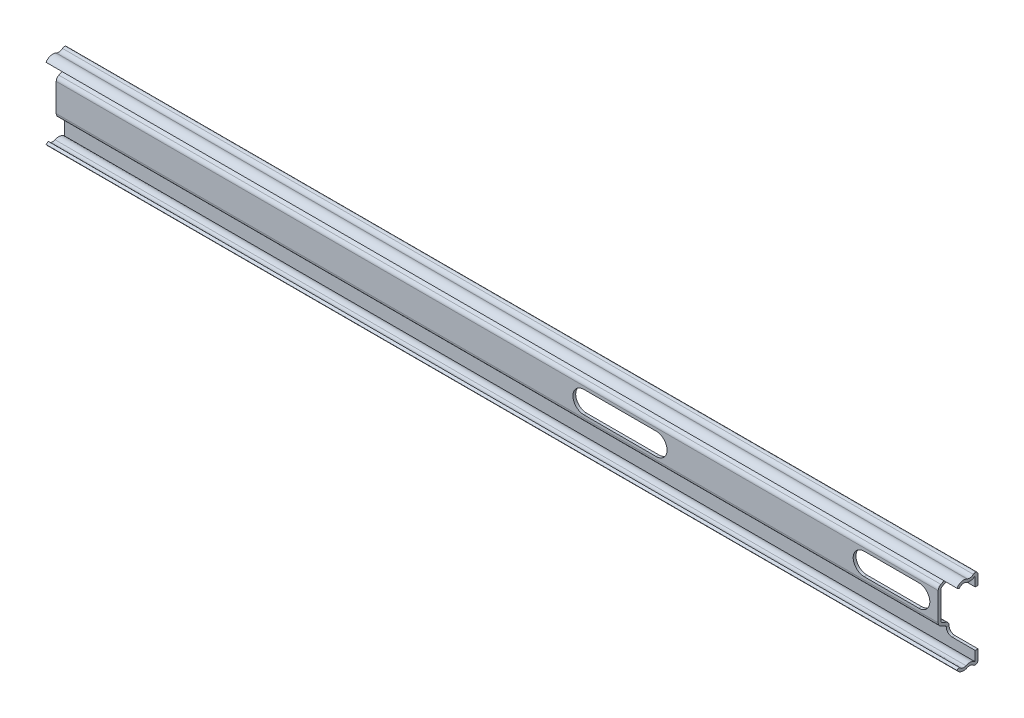
SolidWorks part; units mm, degrees
ref_plane "Front" through (0, 0, 0) normal (0, 0, 1) x (1, 0, 0)
ref_plane "Top" through (0, 0, 0) normal (0, 1, 0) x (1, 0, 0)
ref_plane "Right" through (0, 0, 0) normal (1, 0, 0) x (0, 0, -1)
sketch "Sketch1" plane through (0, 0, 0) normal (1, 0, 0) x (0, 0, -1)
  line L1 (5.6388, 0) -> (-5.6388, 0) construction
  line L4 (-4.1393, 22.8203) -> (-0.7433, 22.6989)
  line L5 (-1.1312, 21.5182) -> (-4.1819, 21.6273)
  line L6 (-4.445, 18.415) -> (-5.6388, 18.415)
  line L7 (-4.445, 21.3734) -> (-4.445, 18.415)
  line L8 (-5.6388, 18.415) -> (-5.6388, 21.3734)
  line L9 (3.9237, 21.6269) -> (0.7619, 21.5441)
  line L10 (5.6388, 0) -> (5.6388, 21.1191)
  line L11 (4.445, 21.1191) -> (4.445, 0)
  line L12 (5.6388, 0) -> (4.445, 0)
  line L13 (-0.7433, 22.6989) -> (3.8925, 22.8203)
  arc A0 (-4.445, 21.3734) -> (-4.1819, 21.6273) centre (-4.191, 21.3734) cw
  arc A1 (-5.6388, 21.3734) -> (-4.1393, 22.8203) centre (-4.191, 21.3734) cw
  arc A3 (3.9237, 21.6269) -> (4.445, 21.1191) centre (3.937, 21.1191) cw
  arc A4 (3.8925, 22.8203) -> (5.6388, 21.1191) centre (3.937, 21.1191) cw
  arc A5 (-1.1312, 21.5182) -> (0.7619, 21.5441) centre (-0.1524, 19.1744) cw
  dimension "D2" = 19.1744
  dimension "D7" = 0.254
  dimension "D8" = 0.508
  dimension "D6" = 2.54
  dimension "D9" = 1.1938
  dimension "D10" = 88.5
  dimension "D1" = 11.2776
  dimension "D3" = 5.7912
  dimension "D4" = 36.83
  dimension "D5" = 1.1938
  dimension "D11" = 87.953
  dimension "D12" = 45.6406
extrude "Extrude1" add sketch "Sketch1" along normal mid plane 400.05
ref_plane "Travel / 2" through (-403.225, 0, 0) normal (-1, 0, 0) x (0, 0, 1)
sketch "Sketch2" plane through (-403.225, 0, 0) normal (-1, 0, 0) x (0, 0, 1)
  line L0 (0.0254, 6.1159) -> (0.0254, 0)
  line L2 (-5.6388, 0) -> (5.6388, 0) construction
  line L3 (5.6388, 21.3734) -> (5.6388, 18.415) construction
  line L7 (-4.445, 21.1191) -> (-4.445, 0) construction
  line L8 (-5.6388, 0) -> (-5.6388, 21.1191) construction
  line L13 (-3.5306, 16.3766) -> (-3.5306, 9.5217)
  line L46 (-2.3867, 7.7262) -> (-0.4146, 6.8065)
  arc A0 (0.0254, 6.1159) -> (-0.4146, 6.8065) centre (-0.7366, 6.1159) ccw
  arc A1 (-1.5056, 17.2916) -> (1.2415, 16.9143) centre (0.1524, 19.1744) ccw
  arc A4 (1.1312, 21.5182) -> (-0.7619, 21.5441) centre (0.1524, 19.1744) ccw construction
  arc A19 (-3.5306, 9.5217) -> (-2.3867, 7.7262) centre (-1.5494, 9.5217) ccw
  arc A25 (-1.5056, 17.2916) -> (-3.5306, 16.3766) centre (-2.3114, 16.3766) ccw
  arc A51 (5.7404, 15.6277) -> (1.2415, 16.9143) centre (2.7686, 13.7451) ccw
  dimension "D2" = 8.4074
  dimension "D3" = 27.4903
  dimension "D6" = 1.9812
  dimension "D8" = 12.2319
  dimension "D10" = 2.5088
  dimension "D11" = 1.2192
  dimension "D4" = 0.762
  dimension "D5" = 4.4704
  dimension "D7" = 115
  dimension "D9" = 19.0435
  dimension "D13" = 11.3792
extrude "Middle Member" add sketch "Sketch2" against normal blind 400.05 separate body thin thin type one direction reverse wall 1.2192
ref_plane "Travel" through (-606.425, 0, 0) normal (-1, 0, 0) x (0, 0, 1)
sketch "Sketch3" plane through (-606.425, 0, 0) normal (-1, 0, 0) x (0, 0, 1)
  line L0 (1.2446, 0) -> (0.0254, 0) construction
  line L1 (-5.6388, 0) -> (-5.6388, 21.1191) construction
  line L56 (7.0612, 0) -> (7.0612, 10.6235)
  line L93 (5.5372, 12.1475) -> (5.1643, 12.1475)
  arc A0 (1.2082, 11.9072) -> (4.2365, 11.8325) centre (2.7686, 13.7451) ccw
  arc A29 (7.0612, 10.6235) -> (5.5372, 12.1475) centre (5.5372, 10.6235) ccw
  arc A53 (5.1643, 12.1475) -> (4.2365, 11.8325) centre (5.1643, 10.6235) ccw
  dimension "D1" = 1.524
  dimension "D4" = 1.524
  dimension "D5" = 2.411
  dimension "D2" = 12.7
  dimension "D3" = 12.1475
  dimension "D6" = 5.853
extrude "Drawer Member" add sketch "Sketch3" against normal blind 400.05 thin thin type one direction wall 1.397
sketch "Sketch6" plane through (0, 0, 7.0612) normal (0, 0, 1) x (1, 0, 0)
  line L1 (-606.425, 0) -> (-604.52, 0)
  line L2 (-606.425, 0) -> (-606.425, 12.1475)
  line L3 (-606.425, 12.1475) -> (-604.52, 12.1475)
  line L4 (-604.52, 0) -> (-604.52, 12.1475)
  line L5 (-206.375, 12.1475) -> (-606.425, 12.1475) construction
  line L7 (-606.425, 10.6235) -> (-606.425, 0) construction
  line L8 (-206.375, 0) -> (-606.425, 0) construction
  dimension "D1" = 1.905
extrude "Cut-Extrude1" cut sketch "Sketch6" against normal through all
sketch "Sketch8" plane through (0, 0, -4.445) normal (0, 0, 1) x (1, 0, 0)
  line L0 (190.3865, 7.6456) -> (191.8208, 7.493)
  line L1 (200.025, 12.2048) -> (190.6284, 12.2048)
  line L2 (191.8208, 7.493) -> (191.8208, 0)
  line L3 (200.025, 0) -> (-200.025, 0) construction
  line L4 (200.025, 21.1191) -> (200.025, 0) construction
  line L5 (200.025, 12.2048) -> (200.025, 0)
  line L6 (200.025, 0) -> (191.8208, 0)
  arc A0 (190.6284, 12.2048) -> (190.3865, 7.6456) centre (190.6284, 9.9188) ccw
  dimension "D3" = 9.9188
  dimension "D1" = 12.2048
  dimension "D2" = 8.2042
  dimension "D4" = 9.3966
  dimension "D5" = 7.493
extrude "Cut-Extrude2" cut sketch "Sketch8" against normal up to next (1.1938 mm away)
sketch "Sketch11" plane through (0, 0, 7.0612) normal (0, 0, 1) x (1, 0, 0)
  line L0 (-212.09, 5.9678) -> (-212.09, 0)
  line L8 (-206.375, 8.5893) -> (-212.2343, 7.2212)
  line L11 (-212.09, 0) -> (-206.375, 0)
  line L12 (-206.375, 0) -> (-206.375, 8.5893)
  arc A1 (-212.2343, 7.2212) -> (-212.09, 5.9678) centre (-212.0899, 6.6028) ccw
  dimension "D3" = 0.635
  dimension "D1" = 5.715
  dimension "D2" = 8.5893
  dimension "D4" = 5.9678
  dimension "D5" = 103.143
extrude "Cut-Extrude3" cut sketch "Sketch11" against normal up to next (1.397 mm away)
sketch "Sketch12" plane through (0, 0, 1.2446) normal (0, 0, 1) x (1, 0, 0)
  line L0 (-3.175, 12.065) -> (-13.335, 12.065)
  line L1 (-3.175, 16.3766) -> (-3.175, 9.5217) construction
  line L2 (-15.875, 9.525) -> (-15.875, 0)
  line L3 (-3.175, 0) -> (-403.225, 0) construction
  line L4 (-15.875, 0) -> (-3.175, 0)
  line L5 (-3.175, 0) -> (-3.175, 12.065)
  arc A0 (-13.335, 12.065) -> (-15.875, 9.525) centre (-13.335, 9.525) ccw
  point P11 (-15.875, 12.065)
  dimension "D3" = 2.54
  dimension "D1" = 12.7
  dimension "D2" = 12.065
extrude "Cut-Extrude4" cut sketch "Sketch12" against normal through all
sketch "Sketch13" plane through (0, 0, -4.445) normal (0, 0, 1) x (1, 0, 0)
  line L0 (-131.6367, 7.112) -> (-156.4652, 7.112)
  line L1 (191.8208, 0) -> (-200.025, 0) construction
  line L2 (-139.7266, 0) -> (-139.7266, 4.2392) construction
  line L3 (-182.5637, 10.287) -> (-131.6367, 10.287)
  line L4 (-200.025, 21.1191) -> (-200.025, 0) construction
  line L5 (-160.2752, 7.112) -> (-182.5637, 7.112)
  line L6 (-159.5132, 0) -> (-159.5132, 6.35)
  line L7 (-157.2272, 6.35) -> (-157.2272, 0)
  line L8 (-137.2501, 2.286) -> (-142.2031, 2.286)
  line L13 (-176.3026, 0) -> (-171.7306, 0)
  line L14 (-168.2, 0) -> (-161.85, 0)
  line L15 (-159.5132, 0) -> (-157.2272, 0)
  line L16 (-154.7126, 0) -> (-150.1406, 0)
  line L17 (-144.4891, 0) -> (-134.9641, 0)
  arc A1 (-182.5637, 10.287) -> (-182.5637, 7.112) centre (-182.5637, 8.6995) ccw
  arc A2 (-159.5132, 6.35) -> (-160.2752, 7.112) centre (-160.2752, 6.35) ccw
  arc A4 (-156.4652, 7.112) -> (-157.2272, 6.35) centre (-156.4652, 6.35) ccw
  arc A7 (-131.6367, 7.112) -> (-131.6367, 10.287) centre (-131.6367, 8.6995) ccw
  arc A8 (-161.85, 0) -> (-168.2, 0) centre (-165.025, 0) ccw
  arc A9 (-171.7306, 0) -> (-176.3026, 0) centre (-174.0166, 0) ccw
  arc A10 (-150.1406, 0) -> (-154.7126, 0) centre (-152.4266, 0) ccw
  arc A11 (-134.9641, 0) -> (-137.2501, 2.286) centre (-137.2501, 0) ccw
  arc A12 (-142.2031, 2.286) -> (-144.4891, 0) centre (-142.2031, 0) ccw
  dimension "D3" = 2.286
  dimension "D4" = 3.175
  dimension "D7" = 8.9916
  dimension "D8" = 21.59
  dimension "D9" = 34.29
  dimension "D10" = 0.762
  dimension "D11" = 17.5387
  dimension "D12" = 9.525
  dimension "D13" = 5.5118
  dimension "D14" = 35
  dimension "D1" = 3.175
  dimension "D2" = 50.927
  dimension "D5" = 2.286
  dimension "D6" = 10.287
extrude "Cut-Extrude5" cut sketch "Sketch13" against normal up to next (1.1938 mm away)
sketch "Sketch32" plane through (0, 0, -5.6388) normal (0, 0, -1) x (-1, 0, 0)
  line L0 (19.5625, 0) -> (29.0875, 0)
  line L1 (33.85, 0) -> (40.2, 0)
  line L2 (43.6925, 0) -> (53.2175, 0)
  line L3 (56.583, 0) -> (61.155, 0)
  line L4 (-191.8208, 0) -> (134.9641, 0) construction
  line L5 (182.5637, 10.287) -> (131.6367, 10.287) construction
  line L6 (131.6367, 7.112) -> (156.4652, 7.112) construction
  line L7 (48.455, 2.286) -> (48.455, -3.4269) construction
  line L8 (24.325, 2.286) -> (24.325, -3.4269) construction
  line L14 (16.3875, 10.287) -> (59.631, 10.287)
  line L15 (55.059, 7.112) -> (16.3875, 7.112)
  line L17 (61.155, 8.763) -> (61.155, 0)
  line L18 (56.583, 0) -> (56.583, 5.588)
  line L23 (21.8485, 2.286) -> (26.8015, 2.286)
  line L25 (45.9785, 2.286) -> (50.9315, 2.286)
  arc A0 (168.2, 0) -> (161.85, 0) centre (165.025, 0) ccw construction
  arc A13 (61.155, 8.763) -> (59.631, 10.287) centre (59.631, 8.763) ccw
  arc A14 (56.583, 5.588) -> (55.059, 7.112) centre (55.059, 5.588) ccw
  arc A17 (16.3875, 10.287) -> (16.3875, 7.112) centre (16.3875, 8.6995) ccw
  arc A20 (29.0875, 0) -> (26.8015, 2.286) centre (26.8015, 0) ccw
  arc A21 (21.8485, 2.286) -> (19.5625, 0) centre (21.8485, 0) ccw
  arc A22 (40.2, 0) -> (33.85, 0) centre (37.025, 0) ccw
  arc A24 (53.2175, 0) -> (50.9315, 2.286) centre (50.9315, 0) ccw
  arc A25 (45.9785, 2.286) -> (43.6925, 0) centre (45.9785, 0) ccw
  dimension "D2" = 1.524
  dimension "D3" = 3.175
  dimension "D4" = 9.525
  dimension "D5" = 2.286
  dimension "D6" = 11.43
  dimension "D7" = 12.7
  dimension "D8" = 24.13
  dimension "D9" = 20.6375
  dimension "D10" = 128
  dimension "D1" = 4.572
extrude "Cut-Extrude14" cut sketch "Sketch32" against normal up to next (1.1938 mm away)
sketch "Sketch33" plane through (83.6094, 0.8125, -5.6388) normal (0, 0, -1) x (-1, 0, 0)
  line L0 (7.1719, -0.8125) -> (16.6969, -0.8125) construction
  line L1 (21.4594, -0.8125) -> (27.8094, -0.8125)
  line L2 (31.3019, -0.8125) -> (40.8269, -0.8125)
  line L3 (44.1924, -0.8125) -> (48.7644, -0.8125)
  line L4 (9.6484, -0.8125) -> (14.2204, -0.8125)
  line L7 (36.0644, 1.4735) -> (36.0644, -4.2394) construction
  line L8 (11.9344, 1.4735) -> (11.9344, -3.4269) construction
  line L9 (-108.2114, -0.8125) -> (103.1719, -0.8125) construction
  line L10 (143.2404, 9.4745) -> (99.9969, 9.4745) construction
  line L11 (99.9969, 6.2995) -> (138.6684, 6.2995) construction
  line L14 (3.9969, 9.4745) -> (47.2404, 9.4745)
  line L15 (42.6684, 6.2995) -> (3.9969, 6.2995)
  line L17 (48.7644, 7.9505) -> (48.7644, -0.8125)
  line L18 (44.1924, -0.8125) -> (44.1924, 4.7755)
  line L23 (9.4579, 1.4735) -> (14.4109, 1.4735) construction
  line L25 (33.5879, 1.4735) -> (38.5409, 1.4735)
  arc A0 (14.2204, -0.8125) -> (9.6484, -0.8125) centre (11.9344, -0.8125) ccw
  arc A1 (251.8094, -0.8125) -> (245.4594, -0.8125) centre (248.6344, -0.8125) ccw construction
  arc A13 (48.7644, 7.9505) -> (47.2404, 9.4745) centre (47.2404, 7.9505) ccw
  arc A14 (44.1924, 4.7755) -> (42.6684, 6.2995) centre (42.6684, 4.7755) ccw
  arc A17 (3.9969, 9.4745) -> (3.9969, 6.2995) centre (3.9969, 7.887) ccw
  arc A20 (16.6969, -0.8125) -> (14.4109, 1.4735) centre (14.4109, -0.8125) ccw construction
  arc A21 (9.4579, 1.4735) -> (7.1719, -0.8125) centre (9.4579, -0.8125) ccw construction
  arc A22 (27.8094, -0.8125) -> (21.4594, -0.8125) centre (24.6344, -0.8125) ccw
  arc A24 (40.8269, -0.8125) -> (38.5409, 1.4735) centre (38.5409, -0.8125) ccw
  arc A25 (33.5879, 1.4735) -> (31.3019, -0.8125) centre (33.5879, -0.8125) ccw
  dimension "D2" = 1.524
  dimension "D3" = 3.175
  dimension "D4" = 9.525
  dimension "D5" = 2.286
  dimension "D6" = 11.43
  dimension "D7" = 12.7
  dimension "D8" = 24.13
  dimension "D9" = 20.6375
  dimension "D10" = 224
  dimension "D1" = 4.572
extrude "Cut F" cut sketch "Sketch33" against normal up to next (1.1938 mm away)
sketch "Sketch34" plane through (169.8236, 1.4527, -5.6388) normal (0, 0, -1) x (-1, 0, 0)
  line L0 (-2.6539, -1.4527) -> (6.8711, -1.4527)
  line L1 (11.6336, -1.4527) -> (17.9836, -1.4527)
  line L2 (21.4761, -1.4527) -> (31.0011, -1.4527)
  line L3 (34.3666, -1.4527) -> (38.9386, -1.4527)
  line L4 (-21.9972, -1.4527) -> (95.8626, -1.4527) construction
  line L7 (26.2386, 0.8333) -> (26.2386, -4.8796) construction
  line L8 (2.1086, 0.8333) -> (2.1086, -4.0671) construction
  line L9 (229.4546, 8.8343) -> (186.2111, 8.8343) construction
  line L10 (186.2111, 5.6593) -> (224.8826, 5.6593) construction
  line L14 (-5.8289, 8.8343) -> (37.4146, 8.8343)
  line L15 (32.8426, 5.6593) -> (-5.8289, 5.6593)
  line L17 (38.9386, 7.3103) -> (38.9386, -1.4527)
  line L18 (34.3666, -1.4527) -> (34.3666, 4.1353)
  line L23 (-0.3679, 0.8333) -> (4.5851, 0.8333)
  line L25 (23.7621, 0.8333) -> (28.7151, 0.8333)
  arc A0 (338.0236, -1.4527) -> (331.6736, -1.4527) centre (334.8486, -1.4527) ccw construction
  arc A13 (38.9386, 7.3103) -> (37.4146, 8.8343) centre (37.4146, 7.3103) ccw
  arc A14 (34.3666, 4.1353) -> (32.8426, 5.6593) centre (32.8426, 4.1353) ccw
  arc A17 (-5.8289, 8.8343) -> (-5.8289, 5.6593) centre (-5.8289, 7.2468) ccw
  arc A20 (6.8711, -1.4527) -> (4.5851, 0.8333) centre (4.5851, -1.4527) ccw
  arc A21 (-0.3679, 0.8333) -> (-2.6539, -1.4527) centre (-0.3679, -1.4527) ccw
  arc A22 (17.9836, -1.4527) -> (11.6336, -1.4527) centre (14.8086, -1.4527) ccw
  arc A24 (31.0011, -1.4527) -> (28.7151, 0.8333) centre (28.7151, -1.4527) ccw
  arc A25 (23.7621, 0.8333) -> (21.4761, -1.4527) centre (23.7621, -1.4527) ccw
  dimension "D2" = 1.524
  dimension "D3" = 3.175
  dimension "D4" = 9.525
  dimension "D5" = 2.286
  dimension "D6" = 11.43
  dimension "D7" = 12.7
  dimension "D8" = 24.13
  dimension "D9" = 20.6375
  dimension "D10" = 320.04
  dimension "D1" = 4.572
extrude "Cut G" cut sketch "Sketch34" against normal up to next (1.1938 mm away)
sketch "Sketch31" plane through (0, 0, -5.6388) normal (0, 0, -1) x (-1, 0, 0)
  line L0 (-200.025, 12.2048) -> (-200.025, 21.1191) construction
  line L1 (-191.8208, 0) -> (-172.4775, 0) construction
  line L2 (-184.15, 0) -> (-177.8, 0)
  arc A0 (-177.8, 0) -> (-184.15, 0) centre (-180.975, 0) ccw
  dimension "D1" = 19.05
  dimension "D2" = 6.35
extrude "Cut-Extrude15" cut sketch "Sketch31" against normal up to next (1.1938 mm away)
sketch "Sketch26" plane through (0, 0, 1.2446) normal (0, 0, 1) x (1, 0, 0)
  line L0 (-176.3026, 0) -> (-134.9641, 0)
  line L1 (-171.4766, 4.826) -> (-139.7901, 4.826)
  line L2 (-19.5625, 0) -> (-53.2175, 0)
  line L3 (-48.3915, 4.826) -> (-24.3885, 4.826)
  line L4 (76.4375, 0) -> (42.7825, 0)
  line L5 (47.6085, 4.826) -> (71.6115, 4.826)
  arc A0 (-176.3026, 0) -> (-171.4766, 4.826) centre (-171.4766, 0) cw
  arc A1 (-134.9641, 0) -> (-139.7901, 4.826) centre (-139.7901, 0) ccw
  arc A2 (-53.2175, 0) -> (-48.3915, 4.826) centre (-48.3915, 0) cw
  arc A3 (-24.3885, 4.826) -> (-19.5625, 0) centre (-24.3885, 0) cw
  arc A4 (-19.5625, 0) -> (-21.8485, 2.286) centre (-21.8485, 0) ccw construction
  arc A5 (-50.9315, 2.286) -> (-53.2175, 0) centre (-50.9315, 0) ccw construction
  arc A6 (42.7825, 0) -> (47.6085, 4.826) centre (47.6085, 0) cw
  arc A7 (71.6115, 4.826) -> (76.4375, 0) centre (71.6115, 0) cw
  dimension "D1" = 4.826
extrude "Cut-Extrude17" cut sketch "Sketch26" against normal up to next (1.2192 mm away)
ref_plane "Plane3" through (-187.325, 0, 0) normal (-1, 0, 0) x (0, 0, 1)
sketch "Sketch27" plane through (-187.325, 0, 0) normal (-1, 0, 0) x (0, 0, 1)
  line L0 (0.1524, 21.6832) -> (0.1524, 16.6656)
  line L1 (0.1524, 23.635) -> (0.1524, 15.2838) construction
  arc A0 (0.1524, 16.6656) -> (0.1524, 21.6832) centre (0.1524, 19.1744) ccw
  arc A1 (-1.5056, 17.2916) -> (1.2415, 16.9143) centre (0.1524, 19.1744) ccw construction
revolve "Revolve1" add sketch "Sketch27" angle 360 about L1
pattern_linear "LPattern1" count 6 spacing 19.05 along (1, 0, 0) of bodies 128
sketch "Sketch28" plane through (-187.325, 0, 0) normal (-1, 0, 0) x (0, 0, 1)
  line L0 (2.6612, 19.1744) -> (-2.3564, 19.1744) construction
  line L1 (3.9624, 18.7934) -> (-3.6576, 18.7934)
  line L2 (3.9624, 18.7934) -> (3.9624, 19.5554)
  line L3 (3.9624, 19.5554) -> (-3.6576, 19.5554)
  line L4 (-3.6576, 18.7934) -> (-3.6576, 19.5554)
  line L5 (0.1524, 20.5465) -> (0.1524, 17.804) construction
  circle A1 centre (0.1524, 19.1744) radius 2.5088 construction
  point P8 (0.1524, 19.1744)
  dimension "D1" = 7.62
  dimension "D2" = 0.762
extrude "Extrude7" add sketch "Sketch28" along normal blind 6.35 and the other way blind 101.6
ref_plane "Plane4" through (-365.125, 0, 0) normal (-1, 0, 0) x (0, 0, 1)
sketch "Sketch29" plane through (-365.125, 0, 0) normal (-1, 0, 0) x (0, 0, 1)
  line L0 (2.7686, 16.0438) -> (2.7686, 11.4464)
  line L1 (2.7686, 16.6801) -> (2.7686, 10.2973) construction
  arc A0 (2.7686, 11.4464) -> (2.7686, 16.0438) centre (2.7686, 13.7451) ccw
  arc A1 (4.7105, 14.9753) -> (1.7707, 15.816) centre (2.7686, 13.7451) ccw construction
revolve "Revolve2" add sketch "Sketch29" angle 360 about L1
pattern_linear "LPattern2" count 6 spacing 19.05 along (1, 0, 0) of bodies 135
sketch "Sketch30" plane through (-365.125, 0, 0) normal (-1, 0, 0) x (0, 0, 1)
  line L0 (0.4699, 13.7451) -> (5.0673, 13.7451) construction
  line L1 (3.9624, 18.7934) -> (3.9624, 19.5554) construction
  line L2 (0.2286, 14.1261) -> (5.3086, 14.1261)
  line L3 (0.2286, 14.1261) -> (0.2286, 13.3641)
  line L4 (0.2286, 13.3641) -> (5.3086, 13.3641)
  line L5 (5.3086, 14.1261) -> (5.3086, 13.3641)
  line L7 (2.7686, 14.2437) -> (2.7686, 12.7853) construction
  circle A0 centre (2.7686, 13.7451) radius 2.2987 construction
  point P4 (2.7686, 13.7451)
  dimension "D1" = 5.08
extrude "Extrude8" add sketch "Sketch30" along normal blind 6.35 and the other way blind 101.6
mirror "Mirror3" about plane through (0, 0, 0) normal (0, 1, 0) of bodies 118 163 159 117 124 126 127 119
mirror "Mirror5" about plane through (0, 0, 0) normal (0, 1, 0) of bodies 141 134
delete or keep bodies "Sólido-Eliminar/Conservar 1" type delete bodies bodies 150
delete or keep bodies "Sólido-Eliminar/Conservar 2" type delete bodies bodies 162
delete or keep bodies "Sólido-Eliminar/Conservar 3" type delete bodies bodies 152
delete or keep bodies "Sólido-Eliminar/Conservar 4" type delete bodies bodies 153
delete or keep bodies "Sólido-Eliminar/Conservar 5" type delete bodies bodies 134
delete or keep bodies "Sólido-Eliminar/Conservar 6" type delete bodies bodies 141
